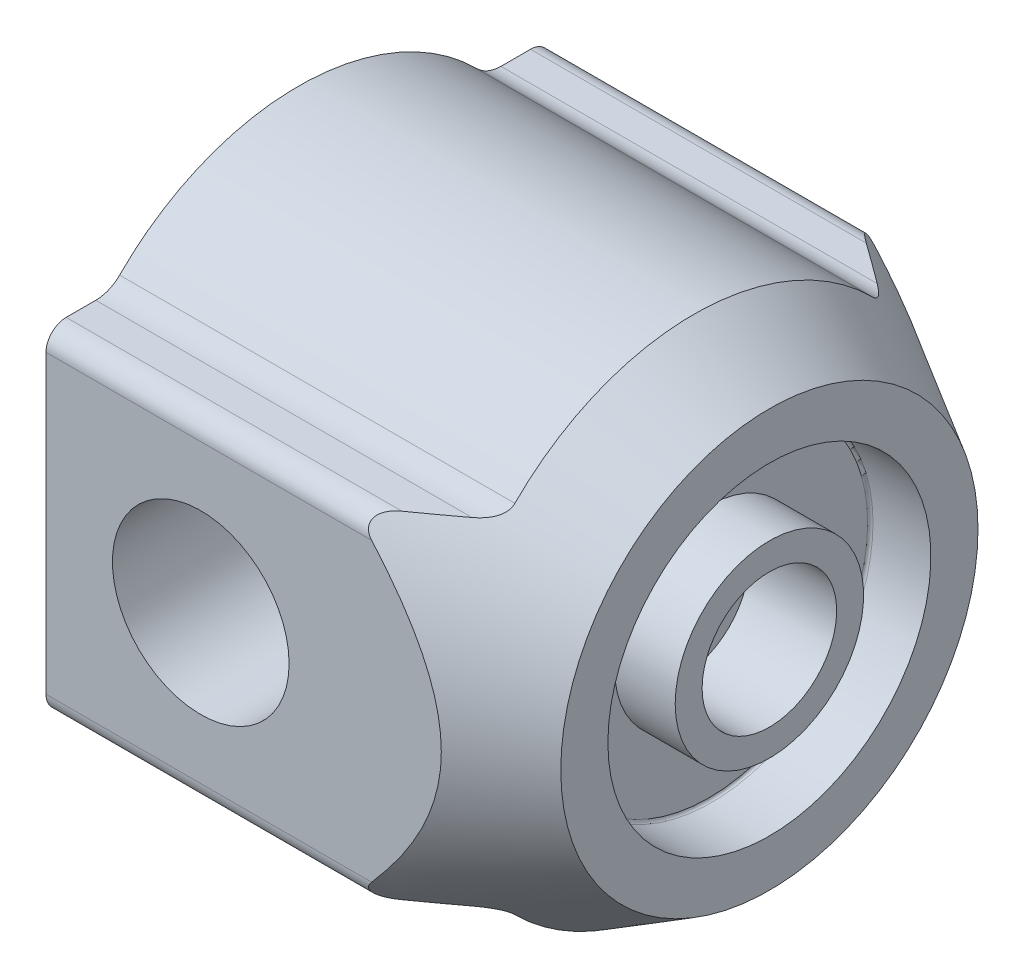
SolidWorks part; units mm, degrees
revolve "Cut-Revolve3" cut sketch "Sketch5" angle 360 about L0
sketch "Sketch5" plane through (24, 0, 0) normal (1, 0, 0) x (0, 0, -1)
  line L0 (0, 0) -> (22.3671, -47.9664) construction
  line L1 (0, 0) -> (0, -59.5073) construction
  line L2 (16.0595, -34.4397) -> (25.1226, -30.2135)
  line L3 (25.1226, -30.2135) -> (24.2773, -28.4009)
  line L4 (24.2773, -28.4009) -> (20.5615, -30.1336)
  line L5 (20.5615, -30.1336) -> (2.8115, 7.9313)
  line L6 (2.8115, 7.9313) -> (-3.9753, 8.5251)
  line L7 (16.0595, -34.4397) -> (-3.9753, 8.5251)
  dimension "D1" = 25
  dimension "D2" = 44
  dimension "D3" = 2
  dimension "D4" = 11.8
  dimension "D5" = 20
  dimension "D6" = 38
  dimension "D7" = 60
cosmetic thread "Cosmetic Thread6"
ref_plane "Front" through (0, 0, 0) normal (0, 0, 1) x (1, 0, 0)
ref_plane "Top" through (0, 0, 0) normal (0, 1, 0) x (1, 0, 0)
ref_plane "Right" through (0, 0, 0) normal (1, 0, 0) x (0, 0, -1)
sketch "Sketch1" plane through (0, 0, 0) normal (0, 0, 1) x (1, 0, 0)
  line L0 (-65.5921, 0) -> (115.6352, 0) construction
  line L1 (0, -45.0387) -> (0, 68.273) construction
  line L2 (-23, 0) -> (-23, 37.5)
  line L3 (-23, 37.5) -> (35.7417, 37.5)
  line L4 (35.7417, 37.5) -> (47, 31)
  line L5 (47, 31) -> (47, 24)
  line L6 (47, 10) -> (34, 10)
  line L7 (34, 10) -> (34, 6)
  line L8 (34, 6) -> (25, 6)
  line L9 (25, 6) -> (21.5359, 0)
  line L10 (47, 24) -> (38, 24)
  line L11 (38, 24) -> (38, 14)
  line L12 (38, 14) -> (47, 14)
  line L13 (47, 14) -> (47, 10)
  line L14 (-23, 0) -> (21.5359, 0)
  circle A0 centre (0, 0) radius 13.5 construction
  dimension "D1" = 27
  dimension "D2" = 47
  dimension "D3" = 70
  dimension "D4" = 75
  dimension "D5" = 62
  dimension "D6" = 48
  dimension "D7" = 28
  dimension "D8" = 20
  dimension "D9" = 12
  dimension "D10" = 60
  dimension "D11" = 9
  dimension "D12" = 30
  dimension "D13" = 13
  dimension "D14" = 22
revolve "Base-Revolve" add sketch "Sketch1" angle 360 about L0
sketch "Sketch2" plane through (0, 0, 0) normal (0, 0, 1) x (1, 0, 0)
  line L0 (-29.4272, 24) -> (47, 24) construction
  line L1 (47, 31) -> (47, -31) construction
  line L2 (-23, 36) -> (-21.5, 36)
  line L3 (-23, 37.5) -> (-23, -37.5) construction
  line L4 (-21.5, 36) -> (-21.5, 31.65)
  line L5 (-21.5, 31.65) -> (39, 31.65)
  line L6 (39, 31.65) -> (43.4167, 24)
  line L7 (-23, 36) -> (-23, 24)
  line L8 (43.4167, 24) -> (-23, 24)
  dimension "D1" = 24
  dimension "D2" = 7.65
  dimension "D3" = 12
  dimension "D4" = 62
  dimension "D5" = 60
  dimension "D6" = 1.5
revolve "Cut-Revolve1" cut sketch "Sketch2" angle 360 about L0
cosmetic thread "Cosmetic Thread5"
sketch "Sketch3" plane through (0, 0, 0) normal (0, 0, 1) x (1, 0, 0)
  line L0 (-27.4404, -24) -> (70.0762, -24) construction
  line L1 (-23, -36) -> (-21.5, -36)
  line L2 (-23, 37.5) -> (-23, -37.5) construction
  line L3 (-21.5, -36) -> (-21.5, -31.65)
  line L4 (-21.5, -31.65) -> (29, -31.65)
  line L5 (29, -31.65) -> (33.4167, -24)
  line L6 (-23, -36) -> (-23, -24)
  line L7 (33.4167, -24) -> (-23, -24)
  dimension "D1" = 24
  dimension "D2" = 1.5
  dimension "D3" = 52
  dimension "D4" = 7.65
  dimension "D5" = 60
  dimension "D6" = 12
revolve "Cut-Revolve2" cut sketch "Sketch3" angle 360 about L0
cosmetic thread "Cosmetic Thread4"
ref_plane "Plane6" through (35.7417, 0, 0) normal (-1, 0, 0) x (0, 0, 1)
sketch "Sketch7" plane through (35.7417, 0, 0) normal (-1, 0, 0) x (0, 0, 1)
  line L0 (-37, 40) -> (-37, -40)
  line L1 (0, 0) -> (0, 44.0698) construction
  line L2 (37, 40) -> (37, -40)
  line L3 (-37, 40) -> (37, 40)
  line L4 (-37, -40) -> (37, -40)
  line L5 (0, 0) -> (-47.3304, 0) construction
  dimension "D1" = 74
  dimension "D2" = 80
extrude "Cut-Extrude4" cut sketch "Sketch7" along normal up to surface (58.7417 mm away) flip side to cut up to face at (-23, -24, 12)
sketch "Sketch8" plane through (-23, 0, 0) normal (-1, 0, 0) x (0, 0, 1)
  line L2 (37, -6.1033) -> (37, 6.1033) construction
  line L3 (-37, 6.1033) -> (-37, -6.1033) construction
  line L4 (-27.9508, 25) -> (-34.5, 25)
  line L5 (-37.5, 22) -> (-37.5, -22)
  line L6 (-34.5, -25) -> (-27.9508, -25)
  line L7 (0, 0) -> (-46.6813, 0) construction
  line L8 (0, 0) -> (0, 42.2152) construction
  line L9 (34.5, -25) -> (27.9508, -25)
  line L10 (27.9508, 25) -> (34.5, 25)
  line L11 (37.5, 22) -> (37.5, -22)
  line L12 (37, -6.1033) -> (37, 6.1033)
  line L13 (-37, 6.1033) -> (-37, -6.1033)
  arc A2 (-37, -6.1033) -> (37, -6.1033) centre (0, 0) ccw construction
  arc A3 (37, 6.1033) -> (-37, 6.1033) centre (0, 0) ccw construction
  arc A4 (-37, -6.1033) -> (-27.9508, -25) centre (0, 0) ccw
  arc A5 (37, 6.1033) -> (27.9508, 25) centre (0, 0) ccw
  arc A6 (-27.9508, 25) -> (-37, 6.1033) centre (0, 0) ccw
  arc A7 (27.9508, -25) -> (37, -6.1033) centre (0, 0) ccw
  arc A8 (-34.5, 25) -> (-37.5, 22) centre (-34.5, 22) ccw
  arc A9 (-37.5, -22) -> (-34.5, -25) centre (-34.5, -22) ccw
  arc A10 (34.5, -25) -> (37.5, -22) centre (34.5, -22) ccw
  arc A11 (34.5, 25) -> (37.5, 22) centre (34.5, 22) cw
  point P17 (-37.5, 25)
  point P20 (-37.5, -25)
  point P23 (37.5, -25)
  point P26 (37.5, 25)
  dimension "D3" = 3
  dimension "D1" = 50
  dimension "D2" = 75
extrude "Extrude4" add sketch "Sketch8" against normal up to surface (58.7417 mm away) up to face at (35.7417, 0, -37.25)
fillet "Fillet2" radius 5 4 edges at (6.3708, 25, 27.9508) (6.3708, -25, 27.9508) (6.3708, -25, -27.9508) (6.3708, 25, -27.9508)
sketch "Sketch4" plane through (0, 0, 0) normal (0, 0, 1) x (1, 0, 0)
  circle A0 centre (0, 0) radius 13.125
  dimension "D1" = 26.25
extrude "Cut-Extrude1" cut sketch "Sketch4" against normal mid plane 90
ref_plane "Plane4" through (24, 0, 0) normal (1, 0, 0) x (0, 0, -1)
fillet "Fillet1" radius 0.4 1 edges at (38, -24, 0)
sketch "Sketch9" plane through (0, 0, 0) normal (0, 0, 1) x (1, 0, 0)
  line L0 (47, 31) -> (35.7417, 37.5) construction
  line L1 (47, 31) -> (7, 54.094)
  line L2 (0, 0) -> (57.2853, 0) construction
  line L3 (7, 54.094) -> (47, 54.094)
  line L4 (47, 54.094) -> (47, 31)
  line L5 (47, -31) -> (47, 31) construction
  dimension "D1" = 40
revolve "Cut-Revolve4" cut sketch "Sketch9" angle 360 about L2
